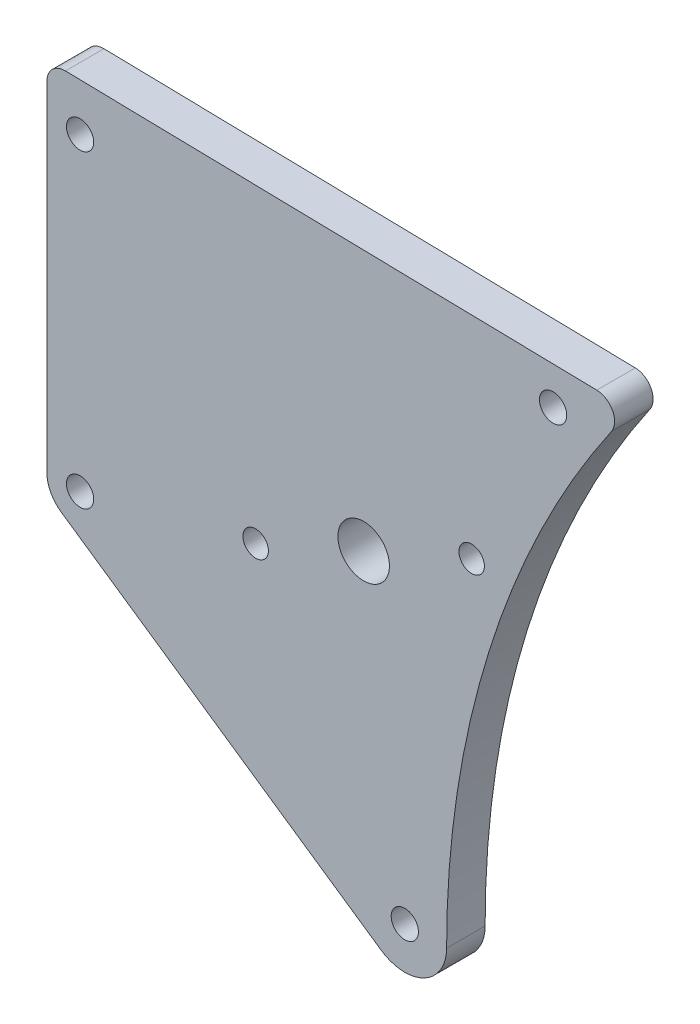
SolidWorks part; units mm, degrees
material "6061 Alloy"
ref_plane "Front Plane" through (0, 0, 0) normal (0, 0, 1) x (1, 0, 0)
ref_plane "Top Plane" through (0, 0, 0) normal (0, 1, 0) x (1, 0, 0)
ref_plane "Right Plane" through (0, 0, 0) normal (1, 0, 0) x (0, 0, -1)
ref_axis "Axis1" through (0, -55, 0) along (0, 1, 0)
sketch "Sketch1" plane through (0, 0, 0) normal (0, 0, 1) x (1, 0, 0)
  line L1 (-164.8576, -5.6845) -> (-217.6068, 30.4834)
  line L6 (-129.3004, 92.0832) -> (-216.9255, 93.8576)
  line L8 (-219.9863, 90.8582) -> (-219.9863, 35)
  circle A1 centre (-185.5543, 42.0469) radius 2.1
  circle A3 centre (-149.9386, 57.6754) radius 2.1
  arc A10 (-126.8903, 87.3823) -> (-129.3004, 92.0832) centre (-129.3612, 89.0838) ccw
  arc A11 (-126.8903, 87.3823) -> (-154.0676, 0) centre (0, 0) ccw
  arc A14 (-216.9255, 93.8576) -> (-219.9863, 90.8582) centre (-216.9863, 90.8582) ccw
  circle A15 centre (-214.51, 86) radius 1.727 construction
  circle A17 centre (-214.51, 35) radius 1.727 construction
  circle A19 centre (-136.51, 86) radius 1.727 construction
  circle A21 centre (-160.96, 0) radius 1.727 construction
  circle A23 centre (-167.7464, 49.8611) radius 4.2488
  arc A24 (-164.8576, -5.6845) -> (-154.0676, 0) centre (-160.96, 0) ccw
  arc A25 (-219.9863, 35) -> (-217.6068, 30.4834) centre (-214.51, 35) ccw
  circle A26 centre (-214.51, 86) radius 2.248
  circle A27 centre (-214.51, 35) radius 2.248
  circle A28 centre (-136.51, 86) radius 2.248
  circle A29 centre (-160.96, 0) radius 2.248
  dimension "D2" = 4.496
extrude "Boss-Extrude1" add sketch "Sketch1" along normal blind 6.35
